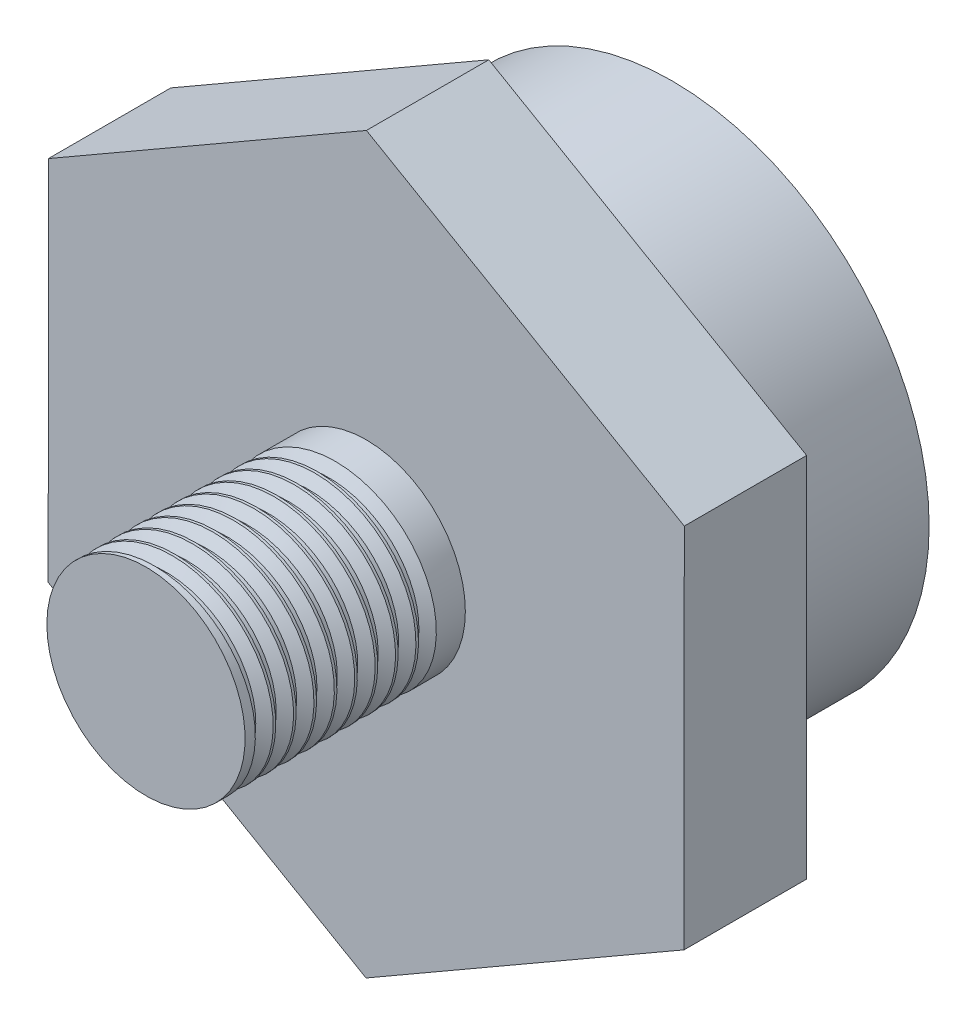
SolidWorks part; units mm, degrees
ref_plane "Front Plane" through (0, 0, 0) normal (0, 0, 1) x (1, 0, 0)
ref_plane "Top Plane" through (0, 0, 0) normal (0, 1, 0) x (1, 0, 0)
ref_plane "Right Plane" through (0, 0, 0) normal (1, 0, 0) x (0, 0, -1)
sketch "Sketch2" plane through (0, 0, 0) normal (0, 0, 1) x (1, 0, 0)
  line L1 (-0.0144, -25.4) -> (21.9898, -12.7125)
  line L2 (21.9898, -12.7125) -> (22.0042, 12.6875)
  line L3 (22.0042, 12.6875) -> (0.0144, 25.4)
  line L4 (0.0144, 25.4) -> (-21.9898, 12.7125)
  line L5 (-21.9898, 12.7125) -> (-22.0042, -12.6875)
  line L6 (-22.0042, -12.6875) -> (-0.0144, -25.4)
  circle A0 centre (0, 0) radius 21.997 construction
  dimension "D1" = 50.8
extrude "Boss-Extrude1" add sketch "Sketch2" along normal blind 8.4667
ref_plane "Plane1" through (0, 0, 0) normal (0, 0, -1) x (-1, 0, 0)
sketch "Sketch4" plane through (0, 0, 0) normal (0, 0, -1) x (-1, 0, 0)
  circle A0 centre (0, 0) radius 17.78
  dimension "D1" = 35.56
extrude "Boss-Extrude2" add sketch "Sketch4" along normal blind 12.7
ref_plane "Plane2" through (0, 0, -12.7) normal (0, 0, -1) x (-1, 0, 0)
sketch "Sketch5" plane through (0, 0, -12.7) normal (0, 0, -1) x (-1, 0, 0)
  circle A0 centre (0, 0) radius 12.7
  dimension "D1" = 25.4
extrude "Cut-Extrude1" cut sketch "Sketch5" against normal blind 11.43
ref_plane "Plane3" through (0, 0, 8.4667) normal (0, 0, 1) x (1, 0, 0)
sketch "Sketch6" plane through (0, 0, 8.4667) normal (0, 0, 1) x (1, 0, 0)
  circle A0 centre (0, 0) radius 6.858
  dimension "D1" = 13.716
extrude "Boss-Extrude3" add sketch "Sketch6" along normal blind 15.24
thread "Thread1" pitch 1.4111 method cut profile "Thread Profile1" start angle 0, offset 0, length 12.7, pitch 1.4111, diameter 13.716
ref_plane "Plane4" through (-6.858, 0, 23.7067) normal (0, -1, 0) x (-1, 0, 0)
sketch "Thread Profile1" plane through (-6.858, 0, 23.7067) normal (0, -1, 0) x (-1, 0, 0)
  line L0 (0, 0) -> (0, 1.4111) construction
  line L11 (0, 0) -> (0, 1.2347)
  line L12 (0, 1.2347) -> (-0.7638, 0.7937)
  line L13 (-0.7638, 0.7937) -> (-0.7638, 0.441)
  line L15 (-0.7638, 0.441) -> (0, 0)
  line L17 (-0.7638, 0.6174) -> (0, 0.6174) construction
  point P2 (0, 0)
  dimension "Pitch" = 1.4111
  dimension "Profile_Angle" = 60
  dimension "Profile_Land" = 0.3528
  dimension "Profile_Height" = 0.7638
